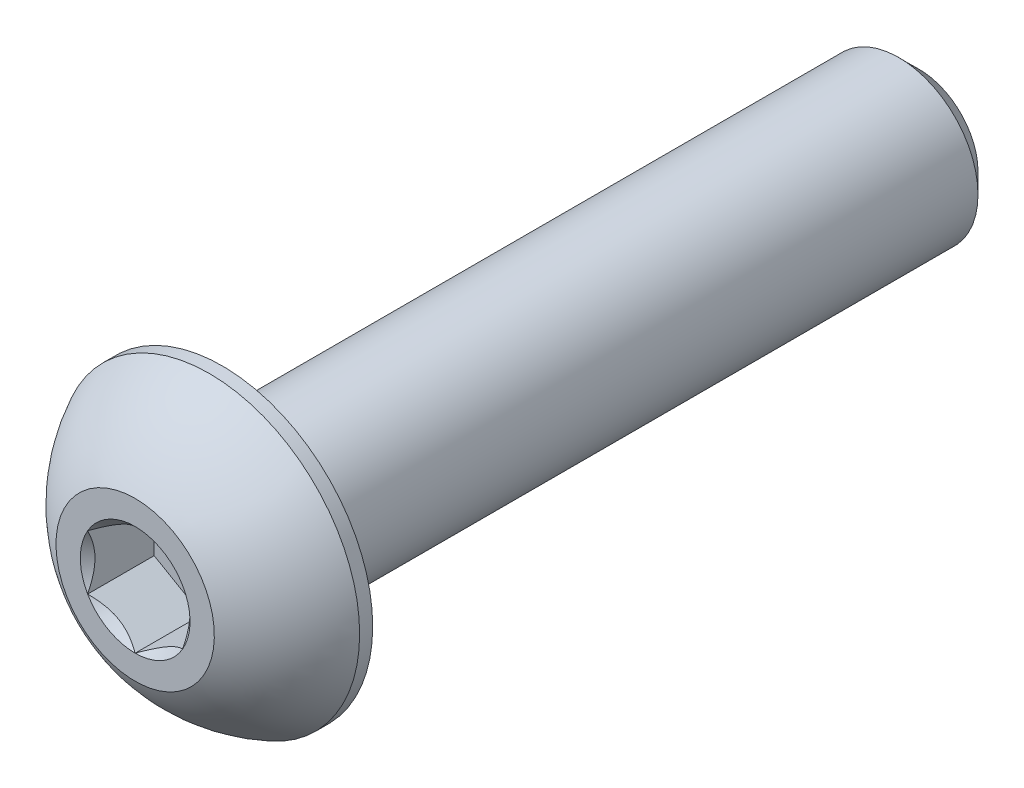
SolidWorks part; units mm, degrees
material "Alloy Steel"
ref_plane "Front Plane" through (0, 0, 0) normal (0, 0, 1) x (1, 0, 0)
ref_plane "Top Plane" through (0, 0, 0) normal (0, 1, 0) x (1, 0, 0)
ref_plane "Right Plane" through (0, 0, 0) normal (1, 0, 0) x (0, 0, -1)
sketch "Sketch1" plane through (0, 0, 0) normal (1, 0, 0) x (0, 0, -1)
  line L0 (-12.375, 0) -> (12.375, 0) construction
  line L1 (-9.625, 4.75) -> (-9.625, -4.75) construction
  line L2 (12.375, 2.5) -> (12.375, -2.5) construction
  line L3 (12.325, 2.5866) -> (12.725, 1.8938) construction
  line L4 (12.725, 1.8938) -> (13.125, 2.5866) construction
  line L5 (13.125, 2.5866) -> (12.325, 2.5866) construction
  line L6 (12.375, 2.5) -> (13.075, 2.5) construction
  line L7 (12.725, 2.5866) -> (12.725, 2.5) construction
  line L8 (12.725, 2.5) -> (12.725, 1.9804) construction
  line L9 (12.725, 1.9804) -> (12.725, 1.8938) construction
  line L10 (12.675, 1.9804) -> (12.775, 1.9804)
  line L11 (12.35, 2.5433) -> (13.1, 2.5433)
  line L12 (12.775, 1.9804) -> (13.1, 2.5433)
  line L13 (12.675, 1.9804) -> (12.35, 2.5433)
  line L14 (-12.375, 1.5) -> (-12.375, -1.5) construction
  line L15 (12.375, 2.5) -> (-9.625, 2.5) construction
  point P3 (-9.625, 0)
  point P6 (-10.275, 0)
  point P21 (12.725, 2.5433)
  point P24 (-10.0375, 4.75)
  point P25 (10.375, -2.5)
  point P26 (-12.375, 2.5)
  dimension "Head Height" = 2.75
  dimension "Length" = 22
  dimension "Head Dia" = 9.5
  dimension "Thread Dia" = 5
  dimension "Pitch" = 0.8
  dimension "D2" = 0.1
  dimension "Drive Size" = 3
  dimension "D1" = 2.1
  dimension "D3" = 0.4125
  dimension "D4" = 2
sketch "Sketch2" plane through (0, 0, 0) normal (1, 0, 0) x (0, 0, -1)
  line L0 (-12.375, 0) -> (12.375, 0)
  line L1 (12.375, 0) -> (12.375, 1.86)
  line L2 (12.375, 2.5) -> (12.375, -2.5) construction
  line L3 (12.375, 1.86) -> (11.735, 2.5)
  line L4 (11.735, 2.5) -> (-9.625, 2.5)
  line L5 (-9.625, 4.75) -> (-9.625, -4.75) construction
  line L6 (-9.625, 2.5) -> (-9.625, 4.75)
  line L7 (-9.625, 4.75) -> (-10.0375, 4.75)
  line L8 (12.375, 2.5) -> (13.075, 2.5) construction
  line L9 (-12.375, 0) -> (-12.375, 2.5)
  arc A0 (-12.375, 2.5) -> (-10.0375, 4.75) centre (-7.7169, 0) cw
  dimension "D1" = 0.64
  dimension "D2" = 45
revolve "Revolve1" add sketch "Sketch2" angle 360 about L0
sketch "Sketch3" plane through (0, 0, 12.375) normal (0, 0, 1) x (1, 0, 0)
  line L1 (0, 1.7321) -> (-1.5, 0.866)
  line L2 (-1.5, 0.866) -> (-1.5, -0.866)
  line L3 (-1.5, -0.866) -> (0, -1.7321)
  line L4 (0, -1.7321) -> (1.5, -0.866)
  line L5 (1.5, -0.866) -> (1.5, 0.866)
  line L6 (1.5, 0.866) -> (0, 1.7321)
  circle A0 centre (0, 0) radius 1.5 construction
  dimension "D1" = 3
extrude "Cut-Extrude1" cut sketch "Sketch3" against normal up to vertex (2.1 mm away) up to point (0, 0, 10.275)
sketch "Sketch4" plane through (0, 0, 12.375) normal (0, 0, 1) x (1, 0, 0)
  circle A0 centre (0, 0) radius 1.7321
extrude "Cut-Extrude2" cut sketch "Sketch4" against normal blind 10 draft 45
split "Split1" [suppressed] bodies to split 106
sketch "Sketch5" [suppressed] plane through (0, 0, -12.375) normal (0, 0, -1) x (-1, 0, 0)
  circle A0 centre (0, 0) radius 2.5 construction
  circle A1 centre (0, 0) radius 2.5
curve "Helix/Spiral1" [suppressed] pitch 0.8 height 22.8 turns 28.5
sketch "Sketch6" [suppressed] plane through (0, 0, 0) normal (1, 0, 0) x (0, 0, -1)
  line L0 (12.675, 1.9804) -> (12.775, 1.9804) construction
  line L1 (12.675, 1.9804) -> (12.35, 2.5433) construction
  line L2 (12.35, 2.5433) -> (13.1, 2.5433) construction
  line L3 (12.775, 1.9804) -> (13.1, 2.5433) construction
  line L4 (12.675, 1.9804) -> (12.775, 1.9804)
  line L5 (12.675, 1.9804) -> (12.35, 2.5433)
  line L6 (12.35, 2.5433) -> (13.1, 2.5433)
  line L7 (12.775, 1.9804) -> (13.1, 2.5433)
sweep "Cut-Sweep1" [suppressed] cut profiles "Sketch6" path "Helix/Spiral1"
sketch "Sketch7" [suppressed] plane through (0, 0, 9.625) normal (0, 0, -1) x (-1, 0, 0)
  circle A1 centre (0, 0) radius 2.5
  circle A2 centre (0, 0) radius 2.5
  dimension "D1" = 0
extrude "Boss-Extrude1" [suppressed] add sketch "Sketch7" along normal blind 10 draft 30
equation "\"D2@Sketch1\" = \"Pitch@Sketch1\" / 8"
equation "\"D1@Sketch1\"=\"Drive Size@Sketch1\"*.7"
equation "\"D3@Sketch1\"=\"Head Height@Sketch1\"*.15"
equation "\"D1@Sketch2\"=\"Pitch@Sketch1\"*.8"
equation "\"D1@Sketch3\"=\"Drive Size@Sketch1\""
equation "\"D4@Helix/Spiral1\"=\"Pitch@Sketch1\""
equation "\"D3@Helix/Spiral1\"=\"Length@Sketch1\"+\"Pitch@Sketch1\""
equation "\"D4@Sketch1\"=\"Pitch@Sketch1\"*2.5"
